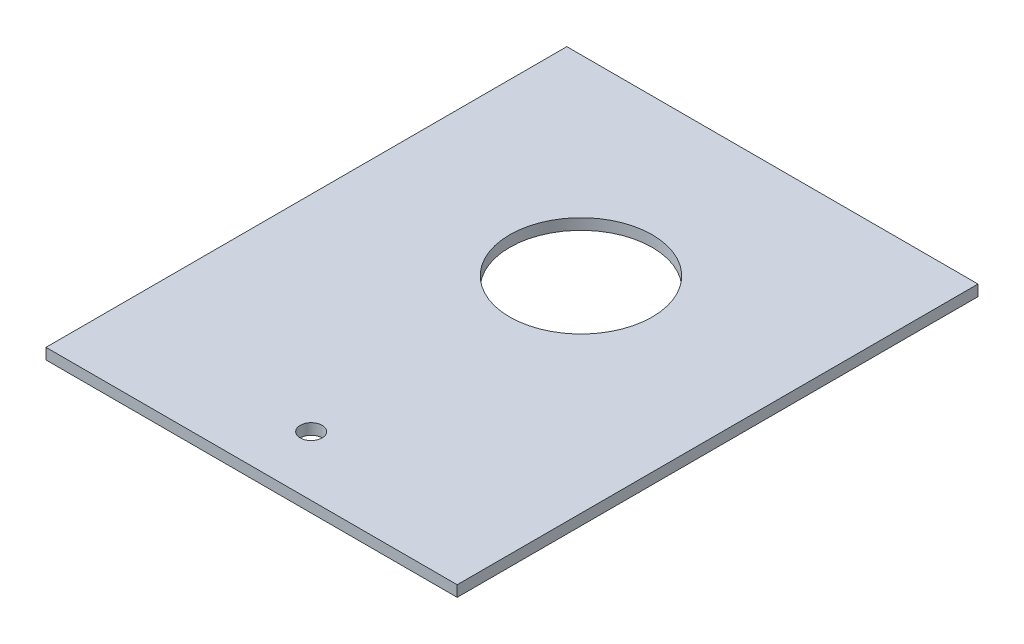
SolidWorks part; units mm, degrees
ref_plane "Front Plane" through (0, 0, 0) normal (0, 0, 1) x (1, 0, 0)
ref_plane "Top Plane" through (0, 0, 0) normal (0, 1, 0) x (1, 0, 0)
ref_plane "Right Plane" through (0, 0, 0) normal (1, 0, 0) x (0, 0, -1)
ref_plane "Plane1" through (0, 32, 0) normal (0, 1, 0) x (1, 0, 0)
sketch "Sketch1" plane through (0, 32, 0) normal (0, 1, 0) x (1, 0, 0)
  line L0 (75, 69.8429) -> (75, -120.1571) construction
  line L1 (-75, -120.1571) -> (75, -120.1571) construction
  line L2 (-75, 69.8429) -> (75, 69.8429) construction
  line L3 (-75, 69.8429) -> (-75, -120.1571) construction
  line L4 (75, 69.8429) -> (75, -120.1571)
  line L5 (-75, -120.1571) -> (75, -120.1571)
  line L6 (-75, 69.8429) -> (75, 69.8429)
  line L7 (-75, 69.8429) -> (-75, -120.1571)
extrude "Boss-Extrude1" add sketch "Sketch1" along normal blind 4
hole_wizard "Hole1" positions "Sketch2" profile "Sketch3" legacy
sketch "Sketch2" plane through (0, 36, 0) normal (0, 1, 0) x (1, 0, 0)
  point P0 (0, 0)
sketch "Sketch3" plane through (0, 36, 0) normal (1, 0, 0) x (0, 0, 1)
  line L0 (0, 0) -> (0, 100)
  line L1 (0, 100) -> (26, 100)
  line L2 (26, 100) -> (26, 0)
  line L3 (26, 0) -> (0, 0)
  line L4 (0, 110) -> (0, -10) construction
  dimension "Diameter" = 52
  dimension "Depth" = 100
hole_wizard "Hole2" positions "Sketch4" profile "Sketch5" legacy
sketch "Sketch4" plane through (0, 36, 0) normal (0, 1, 0) x (1, 0, 0)
  point P0 (0, -98.42)
sketch "Sketch5" plane through (0, 36, 98.42) normal (1, 0, 0) x (0, 0, 1)
  line L0 (0, 0) -> (0, 100)
  line L1 (0, 100) -> (4, 100)
  line L2 (4, 100) -> (4, 0)
  line L3 (4, 0) -> (0, 0)
  line L4 (0, 110) -> (0, -10) construction
  dimension "Diameter" = 8
  dimension "Depth" = 100
